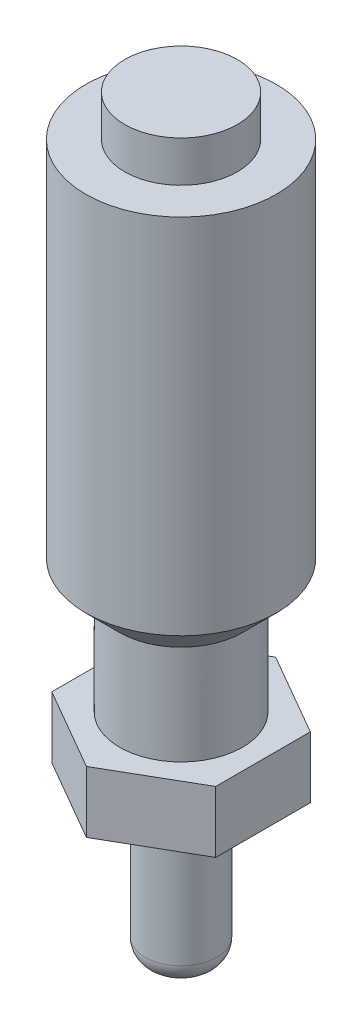
SolidWorks part; units mm, degrees
ref_plane "前视基准面" through (0, 0, 0) normal (0, 0, 1) x (1, 0, 0)
ref_plane "上视基准面" through (0, 0, 0) normal (0, 1, 0) x (1, 0, 0)
ref_plane "右视基准面" through (0, 0, 0) normal (1, 0, 0) x (0, 0, -1)
sketch "草图1" plane through (0, 0, 0) normal (0, 1, 0) x (1, 0, 0)
  circle A0 centre (0, 0) radius 1.75
  dimension "D1" = 3.5
extrude "凸台-拉伸1" add sketch "草图1" along normal blind 7.5
sketch "草图2" plane through (0, 7.5, 0) normal (0, 1, 0) x (1, 0, 0)
  circle A0 centre (0, 0) radius 3
  dimension "D1" = 6
extrude "凸台-拉伸2" add sketch "草图2" along normal blind 7.5
sketch "草图3" plane through (0, 15, 0) normal (0, 1, 0) x (1, 0, 0)
  circle A0 centre (0, 0) radius 4.65
  dimension "D1" = 9.3
extrude "凸台-拉伸3" add sketch "草图3" along normal blind 21.7
fillet "圆角1" radius 1 1 edges at (0, 0, 1.75)
sketch "草图4" plane through (0, 7.5, 0) normal (0, -1, 0) x (1, 0, 0)
  line L1 (0, 4.6188) -> (-4, 2.3094)
  line L2 (-4, 2.3094) -> (-4, -2.3094)
  line L3 (-4, -2.3094) -> (0, -4.6188)
  line L4 (0, -4.6188) -> (4, -2.3094)
  line L5 (4, -2.3094) -> (4, 2.3094)
  line L6 (4, 2.3094) -> (0, 4.6188)
  circle A0 centre (0, 0) radius 4 construction
  dimension "D1" = 8
extrude "凸台-拉伸4" add sketch "草图4" against normal blind 3
sketch "草图5" plane through (0, 36.7, 0) normal (0, 1, 0) x (1, 0, 0)
  circle A0 centre (0, 0) radius 4.65
  circle A1 centre (0, 0) radius 2.75
  dimension "D1" = 5.5
extrude "切除-拉伸1" cut sketch "草图5" against normal blind 2
chamfer "倒角1" distance 2 angle 45 1 edges at (0, 15, 4.65)
